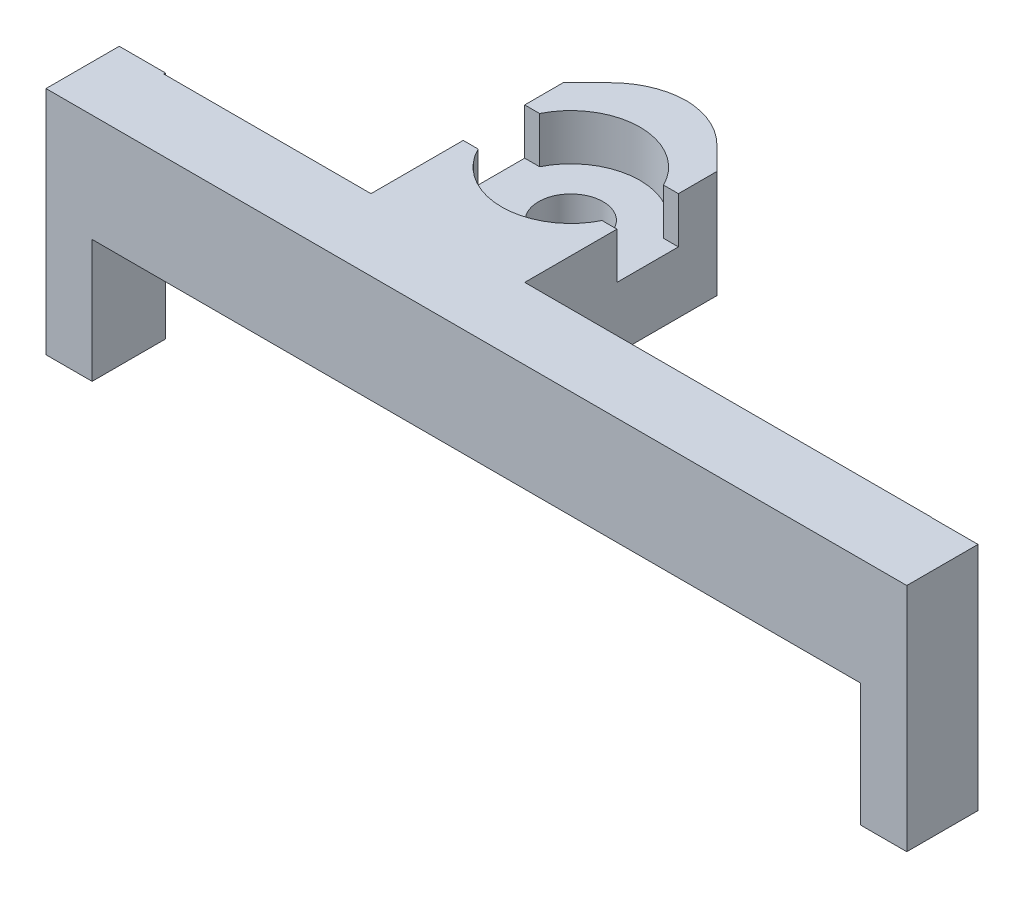
SolidWorks part; units mm, degrees
ref_plane "Front Plane" through (0, 0, 0) normal (0, 0, 1) x (1, 0, 0)
ref_plane "Top Plane" through (0, 0, 0) normal (0, 1, 0) x (1, 0, 0)
ref_plane "Right Plane" through (0, 0, 0) normal (1, 0, 0) x (0, 0, -1)
sketch "Sketch1" plane through (0, 0, 0) normal (0, 1, 0) x (1, 0, 0)
  line L6 (8.0154, -17.1211) -> (-41.9846, -17.1211)
  line L10 (8.0154, -17.1211) -> (8.0154, 82.8789)
  line L11 (8.0154, 82.8789) -> (-41.9846, 82.8789)
  line L12 (-41.9846, -17.1211) -> (-41.9846, 82.8789)
extrude "Boss-Extrude1" add sketch "Sketch1" along normal blind 7
ref_plane "Plane1" through (-16.9846, 0, 0) normal (-1, 0, 0) x (0, 0, 1)
ref_plane "Plane2" through (0, 0, -32.8789) normal (0, 0, 1) x (1, 0, 0)
sketch "Sketch2" plane through (0, 0, 0) normal (0, -1, 0) x (1, 0, 0)
  line L1 (6.0154, -49.8789) -> (11.0415, -49.8789)
  line L2 (-0.4846, -42.2289) -> (-33.4846, -42.2289) construction
  line L3 (-0.4846, -42.2289) -> (-33.4846, -42.2289)
  line L4 (8.0154, -82.8789) -> (8.0154, 17.1211)
  line L5 (8.0154, 17.1211) -> (-41.9846, 17.1211)
  line L6 (-41.9846, 17.1211) -> (-41.9846, -82.8789)
  line L7 (-41.9846, -82.8789) -> (8.0154, -82.8789)
  line L8 (8.0154, -82.8789) -> (8.0154, 17.1211)
  line L9 (8.0154, 17.1211) -> (-41.9846, 17.1211)
  line L10 (-41.9846, 17.1211) -> (-41.9846, -82.8789)
  line L11 (-41.9846, -82.8789) -> (8.0154, -82.8789)
  line L12 (-0.4846, -45.2289) -> (-33.4846, -45.2289)
  line L13 (-39.9846, -49.8789) -> (6.0154, -49.8789)
  line L14 (-28.4914, -50.3789) -> (-28.4914, -65.3789)
  line L15 (6.0154, -65.3789) -> (-39.9846, -65.3789) construction
  line L16 (-28.4914, -65.3789) -> (-18.4914, -65.3789)
  line L17 (-18.4914, -65.3789) -> (-18.4914, -50.3789)
  line L18 (-18.4914, -50.3789) -> (-18.4914, -49.8789)
  line L19 (-28.4914, -50.3789) -> (-28.4914, -49.8789)
  line L20 (11.0415, -49.8789) -> (11.0415, -86.8891)
  line L21 (11.0415, -86.8891) -> (-44.8958, -86.8891)
  line L22 (-44.8958, -86.8891) -> (-44.8958, -49.8789)
  line L23 (-44.8958, -49.8789) -> (-39.9846, -49.8789)
  line M5 (8.0154, -82.8789) -> (8.0154, 17.1211)
  line M8 (-41.9846, -82.8789) -> (8.0154, -82.8789)
  dimension "D4" = 10
  dimension "D1" = 0
  dimension "D2" = 3
extrude "Cut-Extrude1" cut sketch "Sketch2" against normal blind 10 contours L23 L10 L1 L13 L18 L17 L16 L14 L19 M8 M5 region at (-16.31, 0, -67.2861)
sketch "Sketch4" plane through (0, 0, 0) normal (0, -1, 0) x (1, 0, 0)
  line L0 (-0.4846, -42.2289) -> (-33.4846, -42.2289) construction
  line L1 (-0.4846, -42.2289) -> (-33.4846, -42.2289)
  line L2 (-0.4846, -45.2289) -> (-33.4846, -45.2289)
  line L3 (-33.4846, -45.2289) -> (-41.9846, -45.2289)
  line L4 (-41.9846, -49.8789) -> (-41.9846, 17.1211) construction
  line L5 (-41.9846, -45.2289) -> (8.0154, -45.2289)
  line L6 (8.0154, 17.1211) -> (8.0154, -49.8789) construction
  line L7 (8.0154, -45.2289) -> (8.0154, -42.2289)
  line L8 (8.0154, -42.2289) -> (-0.4846, -42.2289)
  line L9 (-33.4846, -42.2289) -> (-41.9846, -42.2289)
  line L10 (-41.9846, -42.2289) -> (-41.9846, -45.2289)
  line M13 (8.0154, -49.8789) -> (8.0154, 17.1211)
  line M15 (-41.9846, 17.1211) -> (-41.9846, -49.8789)
  dimension "D1" = 3
extrude "Cut-Extrude2" cut sketch "Sketch4" against normal blind 28 contours L1 L9 L3 L2 L5 L8 M15 M13 region at (-16.9846, 0, -43.7289)
sketch "Sketch5" plane through (0, 7, 0) normal (0, 1, 0) x (1, 0, 0)
  line L1 (8.0154, 45.2289) -> (11.0154, 45.2289)
  line L2 (8.0154, 45.2289) -> (8.0154, 49.8624)
  line L3 (8.0154, 49.8624) -> (11.0154, 49.8624)
  line L4 (11.0154, 45.2289) -> (11.0154, 49.8624)
  line L5 (-41.9846, 45.2289) -> (-44.9846, 45.2289)
  line L6 (-41.9846, 45.2289) -> (-41.9846, 49.9941)
  line L7 (-41.9846, 49.9941) -> (-44.9846, 49.9941)
  line L8 (-44.9846, 45.2289) -> (-44.9846, 49.9941)
  dimension "D1" = 3
  dimension "D2" = 3
extrude "Boss-Extrude2" add sketch "Sketch5" against normal blind 15 contours L2 L1 L4 L3 | L6 L5 L8 L7
sketch "Sketch6" plane through (0, 7, 0) normal (0, 1, 0) x (1, 0, 0)
  circle A0 centre (-23.4913, 57.8789) radius 2.1
  dimension "D1" = 4.2
extrude "Cut-Extrude3" cut sketch "Sketch6" against normal blind 15
chamfer "Chamfer1" distance 3 angle 45 2 edges at (-18.4914, 3.5, -65.3789) (-28.4914, 3.5, -65.3789)
sketch "Sketch7" plane through (0, 7, 0) normal (0, 1, 0) x (1, 0, 0)
  line L4 (-28.4914, 55.8789) -> (-27.5224, 55.8789)
  line L5 (-28.4914, 59.8789) -> (-27.5224, 59.8789)
  line L6 (-19.4602, 59.8789) -> (-18.4914, 59.8789)
  line L7 (-28.4914, 59.8789) -> (-28.4914, 55.8789)
  line L8 (-18.4914, 55.8789) -> (-18.4914, 59.8789)
  line L10 (-19.4602, 55.8789) -> (-18.4914, 55.8789)
  arc A0 (-19.4602, 59.8789) -> (-27.5224, 59.8789) centre (-23.4913, 57.8789) ccw
  arc A1 (-27.5224, 55.8789) -> (-19.4602, 55.8789) centre (-23.4913, 57.8789) ccw
  dimension "D1" = 9
extrude "Cut-Extrude4" cut sketch "Sketch7" against normal blind 3
fillet "Fillet1" radius 5 2 edges at (-21.4914, 3.5, -65.3789) (-25.4914, 3.5, -65.3789)
sketch "Sketch8" plane through (0, 7, 0) normal (0, 1, 0) x (1, 0, 0)
  line L1 (-43.6987, 44.1422) -> (22.7998, 44.1422)
  line L2 (-43.6987, 44.1422) -> (-43.6987, -21.5537)
  line L3 (-43.6987, -21.5537) -> (22.7998, -21.5537)
  line L4 (22.7998, 44.1422) -> (22.7998, -21.5537)
extrude "Cut-Extrude5" cut sketch "Sketch8" against normal blind 29
